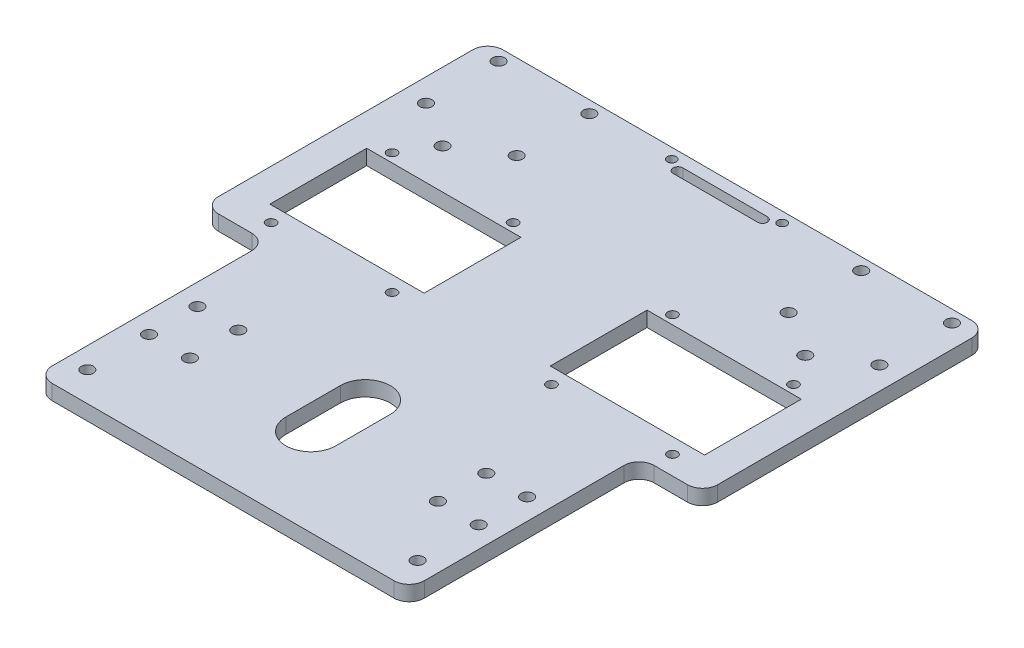
SolidWorks part; units mm, degrees
ref_plane "Front Plane" through (0, 0, 0) normal (0, 0, 1) x (1, 0, 0)
ref_plane "Top Plane" through (0, 0, 0) normal (0, 1, 0) x (1, 0, 0)
ref_plane "Right Plane" through (0, 0, 0) normal (1, 0, 0) x (0, 0, -1)
sketch "Sketch1" plane through (0, 0, 0) normal (0, 1, 0) x (1, 0, 0)
  line L0 (0, 90.99) -> (0, -94.01) construction
  line L1 (-94.5795, 0) -> (90.4205, 0) construction
  line L2 (-82.5, 85) -> (-82.5, -85)
  line L3 (-82.5, -85) -> (82.5, -85)
  line L4 (82.5, -85) -> (82.5, 85)
  line L5 (82.5, 85) -> (-82.5, 85)
  line L6 (-82.5, -9) -> (-82.5, -85)
  line L7 (-82.5, -85) -> (-61.5, -85)
  line L8 (-61.5, -85) -> (-61.5, -9)
  line L9 (-61.5, -9) -> (-82.5, -9)
  line L10 (61.5, -85) -> (61.5, -9)
  line L11 (82.5, -85) -> (61.5, -85)
  line L12 (82.5, -9) -> (82.5, -85)
  line L13 (61.5, -9) -> (82.5, -9)
  dimension "D1" = 82.5
  dimension "D2" = 82.5
  dimension "D3" = 85
  dimension "D4" = 185
  dimension "D5" = 185
  dimension "D6" = 85
  dimension "D7" = 76
  dimension "D8" = 94
  dimension "30" = 21
extrude "Boss-Extrude2" add sketch "Sketch1" along normal blind 5 contours L10 L13 L4 L5 L2 L9 L8 L7 L3 L11 region at (0, 0, -6.0352)
fillet "Fillet8" radius 5 2 edges at (82.5, 2.5, -85) (-82.5, 2.5, -85)
fillet "Fillet9" radius 5 6 edges at (82.5, 2.5, 9) (61.5, 2.5, 9) (61.5, 2.5, 85) (-61.5, 2.5, 85) (-61.5, 2.5, 9) (-82.5, 2.5, 9)
sketch "Sketch4" plane through (0, 5, 0) normal (0, 1, 0) x (1, 0, 0)
  line L0 (0, 0) -> (0, 85) construction
  line L1 (0, 85) -> (0, -85) construction
  line L2 (0, -38) -> (0, -56) construction
  line L3 (-82.5, 38) -> (82.5, 38) construction
  line L4 (-82.5, 80) -> (-82.5, -4) construction
  line L5 (82.5, -4) -> (82.5, 80) construction
  line L6 (-61.5, -80) -> (-61.5, -14) construction
  line L7 (77.5, 85) -> (-77.5, 85) construction
  line L8 (-56.5, -85) -> (56.5, -85) construction
  line L9 (61.5, -80) -> (61.5, -14) construction
  line L10 (-61.5, -47) -> (61.5, -47) construction
  line L13 (8.2559, -38) -> (8.2559, -56)
  line L16 (-8.2559, -38) -> (-8.2559, -56)
  line L17 (-71.8474, 34.3) -> (-20.8474, 34.3)
  line L18 (-20.8474, 34.3) -> (-71.8474, 34.3) construction
  line L19 (-71.8474, 34.3) -> (-71.8474, 2.3) construction
  line L20 (-20.8474, 34.3) -> (-20.8474, 2.3)
  line L21 (-20.8474, 2.3) -> (-71.8474, 2.3)
  line L22 (-71.8474, 2.3) -> (-71.8474, 34.3)
  line L23 (20.8474, 2.3) -> (71.8474, 2.3)
  line L24 (20.8474, 34.3) -> (20.8474, 2.3)
  line L25 (71.8474, 34.3) -> (20.8474, 34.3)
  line L26 (71.8474, 2.3) -> (71.8474, 34.3)
  line L27 (-13.97, 79.3419) -> (13.97, 79.3419) construction
  line L28 (-13.97, 78.3219) -> (-13.97, 80.3619) construction
  line L29 (13.97, 78.3219) -> (13.97, 80.3619) construction
  line L30 (-13.97, 80.9429) -> (13.97, 80.9429)
  line L31 (-13.97, 77.741) -> (13.97, 77.741)
  line L32 (-61.5, -80) -> (-61.5, -14) construction
  line L33 (-56.5, -85) -> (56.5, -85) construction
  line L34 (-82.5, 80) -> (-82.5, -4) construction
  circle A2 centre (-41, -39) radius 2
  circle A10 centre (41, -39) radius 2
  circle A13 centre (41, -55) radius 2
  circle A14 centre (-41, -55) radius 2
  circle A15 centre (-54.5, -39) radius 2
  circle A16 centre (-54.5, -55) radius 2
  circle A17 centre (54.5, -55) radius 2
  circle A18 centre (54.5, -39) radius 2
  arc A23 (8.2559, -38) -> (-8.2559, -38) centre (0, -38) ccw
  arc A24 (-8.2559, -56) -> (8.2559, -56) centre (0, -56) ccw
  circle A25 centre (-66.3474, 37.2) radius 1.605
  circle A26 centre (-26.3474, 37.2) radius 1.605
  circle A27 centre (-66.3474, -2.8) radius 1.605
  circle A28 centre (-26.3474, -2.8) radius 1.605
  circle A29 centre (66.3474, -2.8) radius 1.605
  circle A30 centre (26.3474, -2.8) radius 1.605
  circle A31 centre (26.3474, 37.2) radius 1.605
  circle A32 centre (66.3474, 37.2) radius 1.605
  circle A37 centre (44.945, 81) radius 2
  circle A38 centre (74.945, 81) radius 2
  circle A39 centre (74.945, 57) radius 2
  circle A40 centre (44.945, 57) radius 2
  circle A41 centre (-74.945, 81) radius 2
  circle A42 centre (-74.945, 57) radius 2
  circle A43 centre (-44.945, 57) radius 2
  circle A44 centre (-44.945, 81) radius 2
  circle A46 centre (-18.25, 81.5719) radius 1.5
  circle A47 centre (18.25, 81.5719) radius 1.5
  arc A48 (-13.97, 80.9429) -> (-13.97, 77.741) centre (-13.97, 79.3419) ccw
  arc A49 (13.97, 77.741) -> (13.97, 80.9429) centre (13.97, 79.3419) ccw
  circle A50 centre (-59.945, 47.5) radius 2
  circle A51 centre (-54.599, -75.2963) radius 2
  circle A52 centre (54.599, -75.2963) radius 2
  circle A53 centre (59.945, 47.5) radius 2
  point P50 (0, -47)
  point P110 (0, 79.3419)
  dimension "D2" = 4
  dimension "D13" = 4
  dimension "D10" = 7
  dimension "D11" = 8.2559
  dimension "D5" = 3.21
  dimension "D6" = 4
  dimension "D7" = 3
  dimension "D3" = 16
  dimension "D4" = 16
  dimension "D8" = 4.0571
  dimension "D9" = 13.5
  dimension "D12" = 18
  dimension "D14" = 6.901
  dimension "D15" = 9.7037
  dimension "D16" = 22.555
  dimension "D17" = 37.5
extrude "Cut-Extrude1" cut sketch "Sketch4" against normal blind 5
